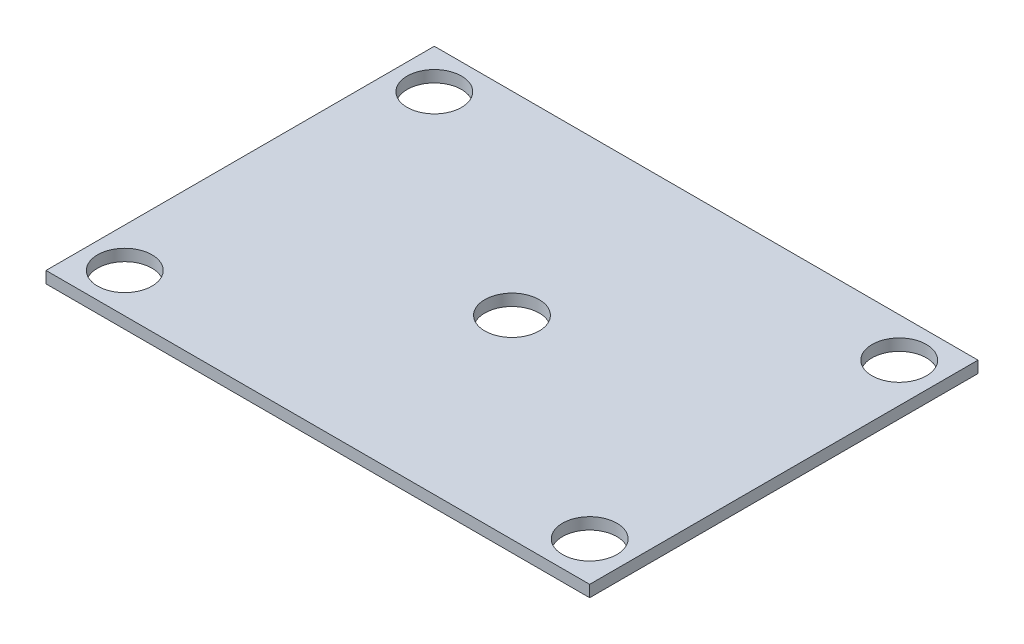
SolidWorks part; units mm, degrees
ref_plane "Front Plane" through (0, 0, 0) normal (0, 0, 1) x (1, 0, 0)
ref_plane "Top Plane" through (0, 0, 0) normal (0, 1, 0) x (1, 0, 0)
ref_plane "Right Plane" through (0, 0, 0) normal (1, 0, 0) x (0, 0, -1)
sketch "Sketch1" plane through (0, 0, 0) normal (0, 1, 0) x (1, 0, 0)
  line L1 (-35, -25) -> (35, -25)
  line L2 (-35, -25) -> (-35, 25)
  line L3 (-35, 25) -> (35, 25)
  line L4 (35, -25) -> (35, 25)
  line L5 (-35, -25) -> (35, 25) construction
  line L6 (-35, 25) -> (35, -25) construction
  point P0 (0, 0)
  dimension "D1" = 70
  dimension "D2" = 50
extrude "Boss-Extrude1" add sketch "Sketch1" along normal blind 1.5
sketch "Sketch2" plane through (0, 1.5, 0) normal (0, 1, 0) x (1, 0, 0)
  circle A0 centre (-29.9289, -19.9289) radius 2.5 construction
  circle A1 centre (29.9289, -19.9289) radius 2.5 construction
  circle A2 centre (0, 0) radius 3.5
  circle A3 centre (-29.9289, 19.9289) radius 2.5 construction
  circle A4 centre (-29.9289, -19.9289) radius 2.5 construction
  circle A5 centre (29.9289, -19.9289) radius 2.5 construction
  circle A7 centre (-29.9289, 19.9289) radius 2.5 construction
  circle A8 centre (29.9289, 19.9289) radius 2.5 construction
  circle A9 centre (29.9289, 19.9289) radius 2.5 construction
  circle A10 centre (-29.9289, 19.9289) radius 3.5
  circle A11 centre (29.9289, 19.9289) radius 3.5
  circle A12 centre (29.9289, -19.9289) radius 3.5
  circle A13 centre (-29.9289, -19.9289) radius 3.5
  circle A14 centre (0, 0) radius 2.5 construction
  dimension "D1" = 1
extrude "Cut-Extrude1" cut sketch "Sketch2" against normal through all
sketch "Sketch3" plane through (0, 1.5, 0) normal (0, 1, 0) x (1, 0, 0)
  line L1 (5.7951, -23) -> (23.7951, -23)
  line L2 (5.7951, -23) -> (5.7951, 23)
  line L3 (5.7951, 23) -> (23.7951, 23)
  line L4 (23.7951, -23) -> (23.7951, 23)
  line L5 (5.7951, -23) -> (23.7951, 23) construction
  line L6 (5.7951, 23) -> (23.7951, -23) construction
  line L7 (-6.7226, -20.6351) -> (-17.8204, -20.6351)
  line L8 (-6.7226, -20.6351) -> (-6.7226, 20.6351)
  line L9 (-6.7226, 20.6351) -> (-17.8204, 20.6351)
  line L10 (-17.8204, -20.6351) -> (-17.8204, 20.6351)
  line L11 (-6.7226, -20.6351) -> (-17.8204, 20.6351) construction
  line L12 (-6.7226, 20.6351) -> (-17.8204, -20.6351) construction
  line L13 (-23.942, -12.539) -> (-32.0968, -12.539)
  line L14 (-23.942, -12.539) -> (-23.942, 12.539)
  line L15 (-23.942, 12.539) -> (-32.0968, 12.539)
  line L16 (-32.0968, -12.539) -> (-32.0968, 12.539)
  line L17 (-23.942, -12.539) -> (-32.0968, 12.539) construction
  line L18 (-23.942, 12.539) -> (-32.0968, -12.539) construction
  point P0 (14.7951, 0)
  point P5 (-28.0194, 0)
  point P11 (-8.8455, 0)
  point P12 (-25.067, 0)
  point P13 (-12.7913, 0)
  point P14 (-12.2715, 0)
  point P19 (-4.7243, 22.5)
  point P20 (-21.384, 11.487)
  point P21 (-28.0194, 0)
  point P22 (-5.99, -18.7702)
  point P23 (-12.2715, 0)
  point P24 (14.7951, 0)
  dimension "D1" = 18
  dimension "D2" = 46
